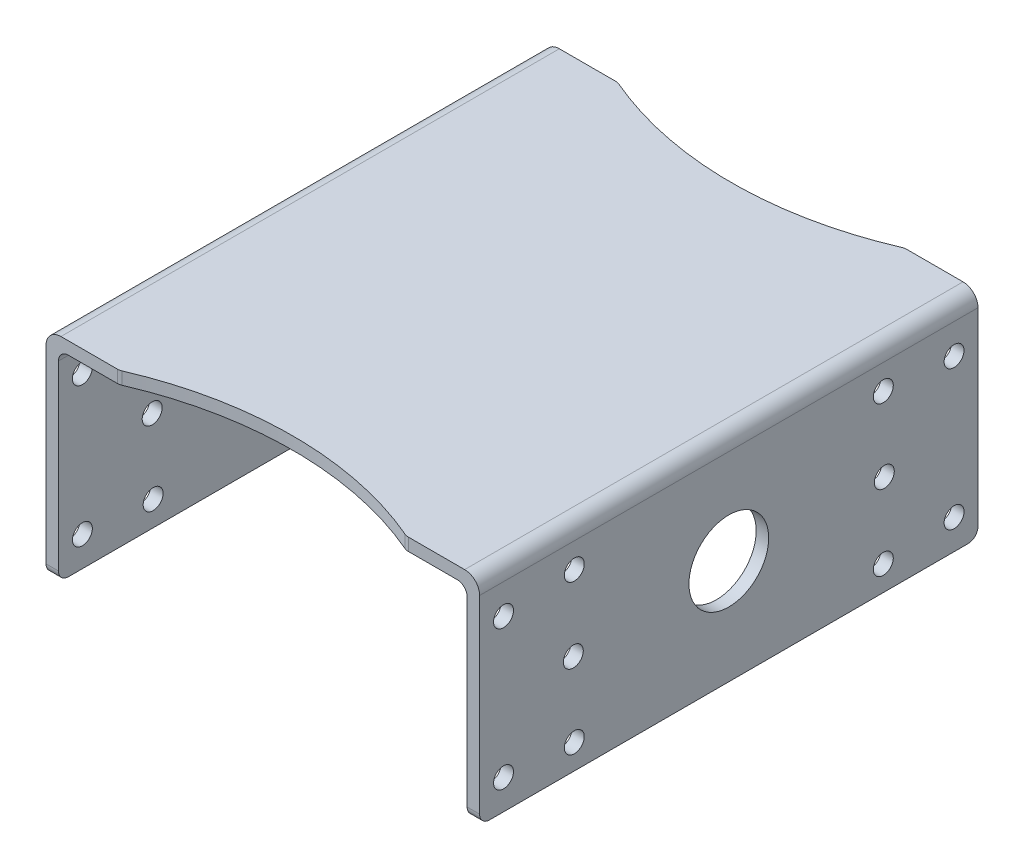
SolidWorks part; units mm, degrees
ref_plane "前视基准面" through (0, 0, 0) normal (0, 0, 1) x (1, 0, 0)
ref_plane "上视基准面" through (0, 0, 0) normal (0, 1, 0) x (1, 0, 0)
ref_plane "右视基准面" through (0, 0, 0) normal (1, 0, 0) x (0, 0, -1)
ref_plane "基准面1" through (0, -20, 0) normal (0, -1, 0) x (1, 0, 0)
sketch "草图1" plane through (0, -20, 0) normal (0, -1, 0) x (1, 0, 0)
  line L0 (21.75, 19) -> (-21.75, 19)
  line L1 (-21.75, 19) -> (-21.75, -31)
  line L2 (-21.75, -31) -> (21.75, -31)
  line L3 (21.75, -31) -> (21.75, 19)
  dimension "D1" = 43.5
  dimension "D2" = 50
extrude "凸台-拉伸1" add sketch "草图1" against normal blind 21.5
sketch "草图2" plane through (0, 0, 19) normal (0, 0, 1) x (1, 0, 0)
  line L0 (-20.5, -22.4182) -> (20.5, -22.4182)
  line L1 (20.5, -22.4182) -> (20.5, 0.25)
  line L2 (20.5, 0.25) -> (-20.5, 0.25)
  line L3 (-20.5, 0.25) -> (-20.5, -22.4182)
  line L4 (0, 1.5) -> (0, -22.4182) construction
  line L5 (21.75, 1.5) -> (-21.75, 1.5) construction
  dimension "D1" = 41
  dimension "D2" = 1.25
extrude "切除-拉伸1" cut sketch "草图2" against normal through all
sketch "草图3" plane through (0, 1.5, 0) normal (0, 1, 0) x (-1, 0, 0)
  line L0 (14.3875, 19) -> (-14.3875, 19)
  arc A0 (-14.3875, 19) -> (14.3875, 19) centre (0, 52) ccw
extrude "切除-拉伸2" cut sketch "草图3" against normal through all
sketch "草图4" plane through (0, 1.5, 0) normal (0, 1, 0) x (-1, 0, 0)
  line L0 (-14.3875, -31) -> (14.3875, -31)
  line L1 (21.75, -31) -> (-21.75, -31) construction
  arc A0 (14.3875, -31) -> (-14.3875, -31) centre (0, -64) ccw
  dimension "D1" = 28.775
extrude "切除-拉伸3" cut sketch "草图4" against normal through all
hole_wizard "Ø2.0 (2) 直径孔1" positions "草图8" profile "草图7" hole size "Ø2.0" standard "ANSI Metric" end condition through all
sketch "草图8" plane through (20.5, 0, 0) normal (-1, 0, 0) x (0, 0, 1)
  line L0 (-21.5, -2.5) -> (-21.5, -17.5) construction
  line L2 (-28.6, -3) -> (-28.6, -17) construction
  line L4 (19, 1.5) -> (19, -20) construction
  line L5 (-31, 1.5) -> (-31, -20) construction
  point P0 (16.6, -3)
  point P1 (16.6, -17)
  point P2 (9.5, -17.5)
  point P3 (9.6, -10)
  point P4 (9.5, -2.5)
  point P5 (-21.5, -2.5)
  point P6 (-28.6, -3)
  point P7 (-28.6, -17)
  point P8 (-21.5, -17.5)
  point P9 (-21.6, -10)
  dimension "D1" = 14
  dimension "D2" = 7.5
  dimension "D3" = 7.5
  dimension "D4" = 7.1
  dimension "D5" = 0.1
  dimension "D6" = 2.4
  dimension "D7" = 2.4
sketch "草图7" plane through (20.5, -3, 16.6) normal (0, 1, 0) x (0, 0, 1)
  line L0 (0, 0) -> (0, 1.25)
  line L1 (0, 1.25) -> (1, 1.25)
  line L2 (1, 1.25) -> (1, 0)
  line L5 (1, 0) -> (0, 0)
  line L11 (0, -6.35) -> (0, 107.95) construction
  dimension "通孔孔直径" = 2
  dimension "通孔孔深度" = 1.25
hole_wizard "Ø2.0 (2) 直径孔2" positions "草图12" profile "草图11" hole size "Ø2.0" standard "ANSI Metric"
sketch "草图12" plane through (-20.5, 0, 0) normal (1, 0, 0) x (0, 0, -1)
  line L0 (21.5, -2.5) -> (21.5, -17.5) construction
  line L2 (28.6, -3) -> (28.6, -17) construction
  line L4 (31, 1.5) -> (31, -20) construction
  point P0 (-16.6, -3)
  point P1 (-16.6, -17)
  point P2 (-9.5, -17.5)
  point P3 (-9.6, -10)
  point P4 (-9.5, -2.5)
  point P5 (21.5, -2.5)
  point P6 (28.6, -3)
  point P7 (28.6, -17)
  point P8 (21.5, -17.5)
  point P9 (21.6, -10)
  dimension "D1" = 7.1
  dimension "D2" = 0.1
  dimension "D3" = 14
  dimension "D4" = 15
  dimension "D5" = 7.5
  dimension "D6" = 2.4
sketch "草图11" plane through (-20.5, -3, 16.6) normal (0, 1, 0) x (0, 0, -1)
  line L0 (0, 0) -> (0, 1.25)
  line L1 (0, 1.25) -> (1, 1.25)
  line L2 (1, 1.25) -> (1, 0)
  line L5 (1, 0) -> (0, 0)
  line L11 (0, -6.35) -> (0, 107.95) construction
  dimension "通孔孔直径" = 2
  dimension "通孔孔深度" = 1.25
fillet "圆角1" radius 1 8 edges at (14.3875, 0.875, 19) (21.125, -20, 19) (-14.3875, 0.875, -31) (14.3875, 0.875, -31) (-21.125, -20, -31) (21.125, -20, -31) (-21.125, -20, 19) (-14.3875, 0.875, 19) tangent propagation no
fillet "圆角2" radius 1.5 2 edges at (21.75, 1.5, -6) (-21.75, 1.5, -6) tangent propagation no
sketch "草图13" plane through (21.75, 0, 0) normal (1, 0, 0) x (0, 0, -1)
  line L0 (-19, -9.5) -> (31, -9.5) construction
  line L1 (-19, 0) -> (-19, -19) construction
  line L2 (31, 0) -> (31, -19) construction
  line L3 (6, 0) -> (6, -20) construction
  line L4 (31, 0) -> (-19, 0) construction
  line L5 (30, -20) -> (-18, -20) construction
  circle A0 centre (6, -9.5) radius 4
  dimension "D1" = 8
extrude "切除-拉伸4" cut sketch "草图13" against normal through all
fillet "圆角3" radius 1 2 edges at (20.5, 0.25, -6) (-20.5, 0.25, -6)
